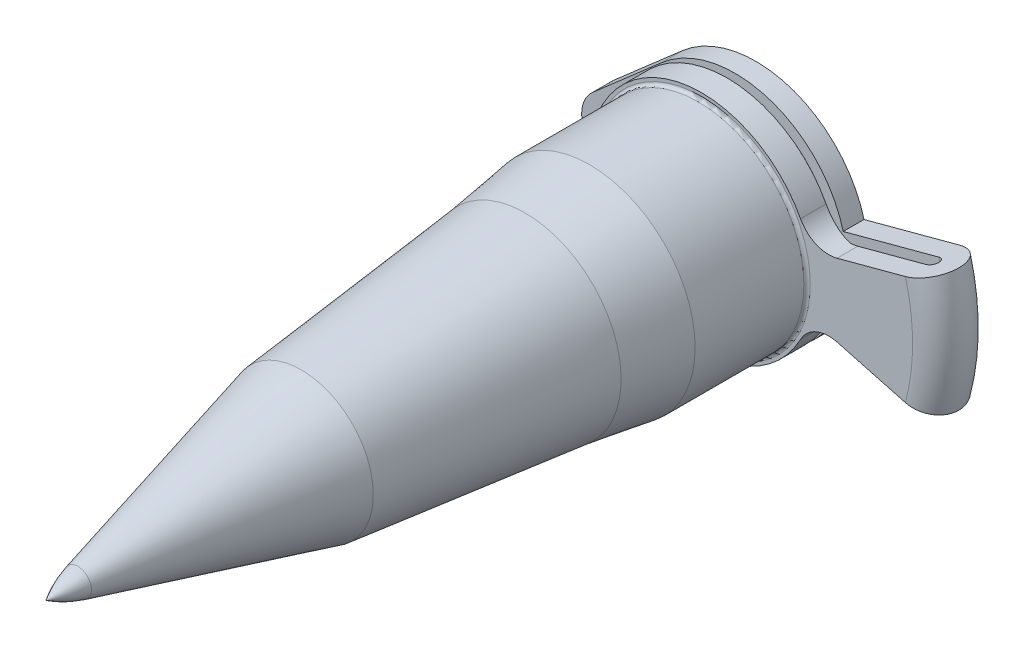
SolidWorks part; units mm, degrees
ref_plane "Front Plane" through (0, 0, 0) normal (0, 0, 1) x (1, 0, 0)
ref_plane "Top Plane" through (0, 0, 0) normal (0, 1, 0) x (1, 0, 0)
ref_plane "Right Plane" through (0, 0, 0) normal (1, 0, 0) x (0, 0, -1)
sketch "Sketch1" plane through (0, 0, 0) normal (0, 0, 1) x (1, 0, 0)
  circle A0 centre (0, 0) radius 3.5
  circle A1 centre (0, 0) radius 3.15
  dimension "D1" = 7
  dimension "D2" = 6.3
extrude "Boss-Extrude1" add sketch "Sketch1" along normal blind 0.8
sketch "Sketch5" plane through (0, 0, 0) normal (0, 1, 0) x (1, 0, 0)
  line L0 (3.3, -0.8) -> (3.15, -0.8)
  line L1 (3.3, -4.3) -> (3, -6.3154)
  line L2 (3, -6.3154) -> (2.25, -13.3154)
  line L3 (2.25, -13.3154) -> (0.4272, -20.3054)
  line L4 (3.3, -0.8) -> (3.3, -4.3)
  line L5 (3.15, -0.8) -> (3.15, -4.2889)
  line L12 (3.15, -4.2889) -> (2.8483, -6.3154)
  line L13 (2.8483, -6.3154) -> (2.0983, -13.3154)
  line L16 (2.0983, -13.3154) -> (0.2756, -20.3054)
  line L18 (0, 0) -> (0, -27.5334) construction
  line L19 (0, -21.3) -> (0, -21.2195)
  line L20 (0, -21.2195) -> (0.2756, -20.3054)
  arc A0 (0.4272, -20.3054) -> (0, -21.3) centre (-3.0629, -19.3953) cw
  point P7 (0, 0)
  point P15 (-0.1612, -20.152)
  point P16 (-3.0629, -19.3953)
  point P17 (-0.675, -21.2093)
  dimension "D1" = 3.5
  dimension "D2" = 20.5
  dimension "D3" = 3.3
  dimension "D4" = 0.15
  dimension "D6" = 3
  dimension "D7" = 8.5
  dimension "D8" = 2.25
  dimension "D9" = 7
  dimension "D10" = 0.15
revolve "Revolve7" add sketch "Sketch5" angle 360 about L18
fillet "Fillet2" radius 0.1 1 edges at (-3.3, 0, 0.8)
sketch "Sketch6" plane through (0, 0, 0) normal (0, 1, 0) x (1, 0, 0)
  line L0 (3.5, -0.8) -> (3.5, 0)
  line L1 (6.6, 0.9) -> (3.5, 0.9)
  line L2 (3.5, -0.8) -> (6.6, -0.8)
  line L3 (4.15, -0.15) -> (3.5, 0)
  line L4 (4.15, -0.15) -> (6.6, -0.15)
  line L5 (6.6, 0.25) -> (3.5, 0.25)
  line L6 (4.15, -0.15) -> (4.15, 0) construction
  line L7 (3.5, 0.9) -> (3.5, 0.25)
  arc A0 (6.6, -0.8) -> (6.6, 0.9) centre (6.6, 0.05) ccw
  arc A1 (6.6, -0.15) -> (6.6, 0.25) centre (6.6, 0.05) ccw
  dimension "D1" = 3.1
  dimension "D2" = 1.7
  dimension "D3" = 0.65
ref_axis "Axis3" through (0, 0, 4.2889) along (0, 0, -1)
revolve "Revolve8" add sketch "Sketch6" angle 30 mid plane about axis through (0, 0, 4.2889) along (0, 0, -1)
fillet "Fillet9" radius 1 1 edges at (3.3807, 0.9059, 0.4)
fillet "Fillet10" radius 1 1 edges at (3.3807, -0.9059, 0.4)
sketch "Sketch8" plane through (0, 0, -0.9) normal (0, 0, -1) x (-1, 0, 0)
  line L0 (2.3026, -2.6359) -> (4.4579, -0.7531)
  line L1 (4.4579, 0.7531) -> (2.3026, 2.6359)
  line L2 (4.8, 0) -> (-3.5, 0) construction
  arc A0 (-3.0949, -1.6345) -> (-3.0949, 1.6345) centre (0, 0) ccw construction
  arc A1 (-3.0949, -1.6345) -> (2.3026, -2.6359) centre (0, 0) ccw
  arc A2 (4.4579, 0.7531) -> (4.4579, -0.7531) centre (3.8, 0) cw
  arc A3 (2.3026, 2.6359) -> (-3.0949, -1.6345) centre (0, 0) ccw
  point P13 (4.8, 0)
  dimension "D1" = 1
  dimension "D2" = 8.3
extrude "Boss-Extrude2" add sketch "Sketch8" against normal up to vertex (0.65 mm away) up to point (3.3807, 0.9059, -0.25)
sketch "Sketch9" plane through (0, 0, -0.25) normal (0, 0, 1) x (1, 0, 0)
  circle A0 centre (0, 0) radius 3.15
  circle A1 centre (0, 0) radius 2.55
  circle A2 centre (0, 0) radius 3.15 construction
  circle A3 centre (0, 0) radius 3.15 construction
  dimension "D1" = 0.6
extrude "Boss-Extrude3" add sketch "Sketch9" along normal blind 2.63
sketch "Sketch10" plane through (0, 0, -0.25) normal (0, 0, 1) x (1, 0, 0)
  circle A0 centre (0, 0) radius 1.25
  circle A1 centre (0, 0) radius 1.1
  dimension "D1" = 2.5
  dimension "D2" = 0.15
extrude "Boss-Extrude4" add sketch "Sketch10" along normal blind 0.4
